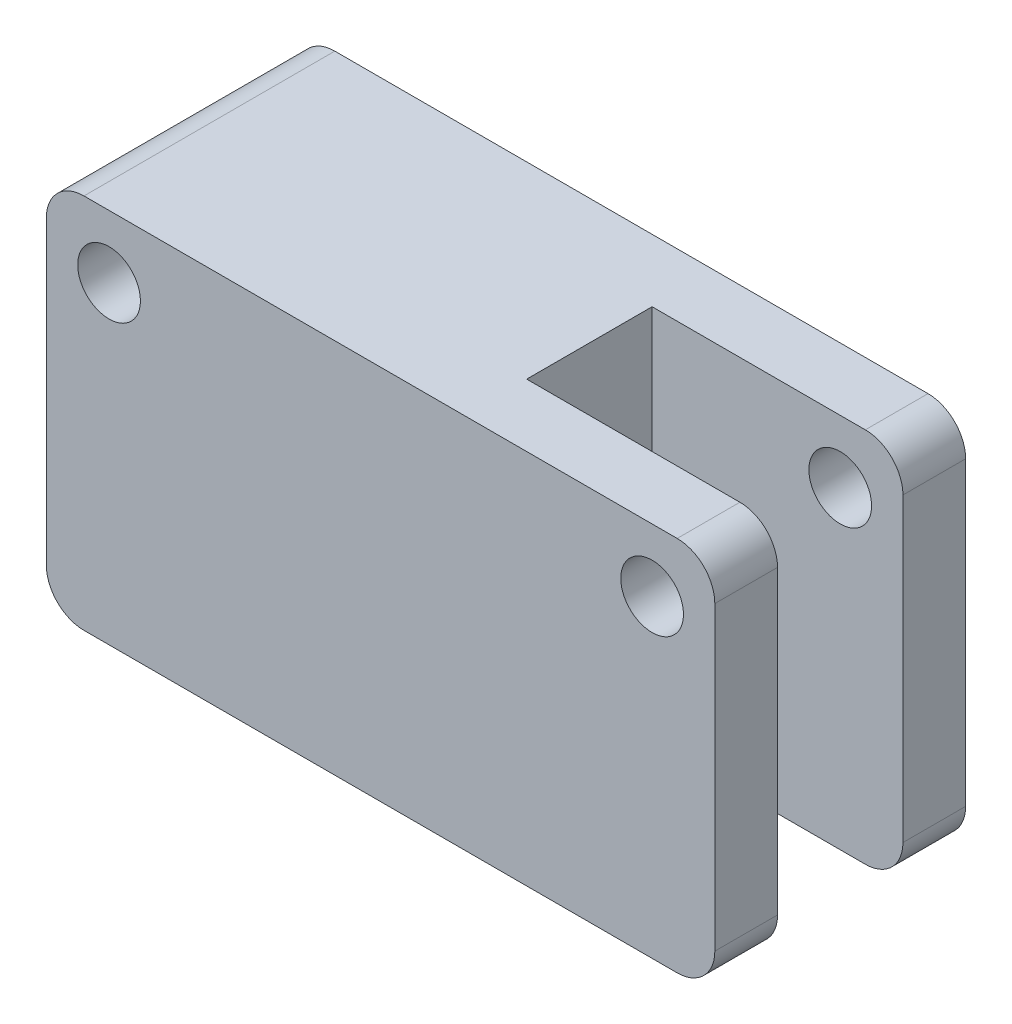
SolidWorks part; units mm, degrees
ref_plane "Plan de face" through (0, 0, 0) normal (0, 0, 1) x (1, 0, 0)
ref_plane "Plan de dessus" through (0, 0, 0) normal (0, 1, 0) x (1, 0, 0)
ref_plane "Plan de droite" through (0, 0, 0) normal (1, 0, 0) x (0, 0, -1)
other "Centre de masse"
sketch "Esquisse2" plane through (0, 0, 0) normal (0, 1, 0) x (1, 0, 0)
  line L0 (0, 0) -> (56.0293, 0) construction
  line L1 (0, -10) -> (53.3, -10)
  line L2 (0, -10) -> (0, 10)
  line L3 (0, 10) -> (53.3, 10)
  line L4 (53.3, -10) -> (53.3, 10)
  line L5 (0, 0) -> (0, -42.7765) construction
  dimension "D1" = 53.3
extrude "Boss.-Extru.1" add sketch "Esquisse2" along normal mid plane 30
fillet "Congé1" radius 3 4 edges at (0, 15, 0) (53.3, 15, 0) (53.3, -15, 0) (0, -15, 0)
sketch "Esquisse4" plane through (0, 15, 0) normal (0, 1, 0) x (1, 0, 0)
  line L0 (53.3, 10) -> (53.3, -10) construction
  line L1 (53.3, 5) -> (53.3, -5)
  line L2 (53.3, -5) -> (33.3, -5)
  line L4 (33.3, -5) -> (33.3, 5)
  line L6 (33.3, 5) -> (53.3, 5)
  line L7 (3, -10) -> (50.3, -10) construction
  line L8 (63.6485, 0) -> (81.8664, 0) construction
  dimension "D1" = 20
  dimension "D2" = 5
extrude "Enlèv. mat.-Extru.1" cut sketch "Esquisse4" against normal through all
sketch "Esquisse5" plane through (0, 0, -10) normal (0, 0, -1) x (-1, 0, 0)
  line L0 (-50.3, 15) -> (-3, 15) construction
  line L1 (-53.3, 12) -> (-53.3, -12) construction
  line L2 (-26.65, 0) -> (-26.65, 9.0949) construction
  circle A0 centre (-48.3, 10) radius 2.5
  circle A1 centre (-5, 10) radius 2.5
  dimension "D1" = 5
  dimension "D2" = 5
  dimension "D3" = 5
  dimension "D4" = 26.65
extrude "Enlèv. mat.-Extru.2" cut sketch "Esquisse5" against normal through all
ref_axis "Axe1" through (5, 10, 10) along (0, 0, -1)
ref_point "Point1"
equation "\"L\"= 0.02m"
equation "\"ldoigt\"= 0.0533m"
equation "\"D1@Esquisse2\"=\"ldoigt\""
equation "\"D2@Esquisse2\"=\"L\""
equation "\"e\"= 0.03m"
equation "\"D1@Congé1\"=\"e\"/10m"
equation "\"D4@Esquisse5\"=\"ldoigt\"/2"
